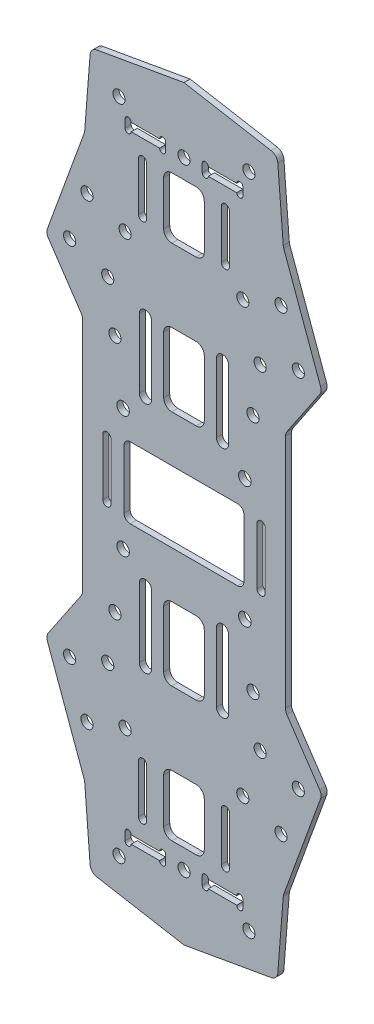
SolidWorks part; units mm, degrees
ref_plane "Front Plane" through (0, 0, 0) normal (0, 0, 1) x (1, 0, 0)
ref_plane "Top Plane" through (0, 0, 0) normal (0, 1, 0) x (1, 0, 0)
ref_plane "Right Plane" through (0, 0, 0) normal (1, 0, 0) x (0, 0, -1)
sketch "Sketch1" plane through (0, 0, 0) normal (0, 0, 1) x (1, 0, 0)
  line L0 (20, 7) -> (20, -7)
  line L1 (18, -7) -> (18, 7)
  line L2 (-18, 7) -> (-18, -7)
  line L3 (-20, -7) -> (-20, 7)
  line L4 (-11.2, -70.25) -> (-11.2, -58.25)
  line L5 (-9.2, -58.25) -> (-9.2, -70.25)
  line L6 (-11, -37.25) -> (-11, -20.25)
  line L7 (-8, -20.25) -> (-8, -37.25)
  line L8 (8, -37.25) -> (8, -20.25)
  line L9 (11, -20.25) -> (11, -37.25)
  line L10 (9.2, -70.25) -> (9.2, -58.25)
  line L11 (11.2, -58.25) -> (11.2, -70.25)
  line L12 (-3, -20.25) -> (3, -20.25)
  line L13 (5, -22.25) -> (5, -36.25)
  line L14 (3, -38.25) -> (-3, -38.25)
  line L15 (-5, -36.25) -> (-5, -22.25)
  line L16 (5, -58.25) -> (5, -69.25)
  line L17 (3, -71.25) -> (-3, -71.25)
  line L18 (-5, -69.25) -> (-5, -58.25)
  line L19 (-3, -56.25) -> (3, -56.25)
  line L20 (11.2, 70.25) -> (11.2, 58.25)
  line L21 (9.2, 58.25) -> (9.2, 70.25)
  line L22 (11, 37.25) -> (11, 20.25)
  line L23 (8, 20.25) -> (8, 37.25)
  line L24 (-8, 37.25) -> (-8, 20.25)
  line L25 (-11, 20.25) -> (-11, 37.25)
  line L26 (-9.2, 70.25) -> (-9.2, 58.25)
  line L27 (-11.2, 58.25) -> (-11.2, 70.25)
  line L28 (13.25, -8.75) -> (-13.25, -8.75)
  line L29 (-14.75, -7.25) -> (-14.75, 7.25)
  line L30 (-13.25, 8.75) -> (13.25, 8.75)
  line L31 (14.75, 7.25) -> (14.75, -7.25)
  line L32 (-5, 58.25) -> (-5, 69.25)
  line L33 (-3, 71.25) -> (3, 71.25)
  line L34 (5, 69.25) -> (5, 58.25)
  line L35 (3, 56.25) -> (-3, 56.25)
  line L36 (-3, 38.25) -> (3, 38.25)
  line L37 (5, 36.25) -> (5, 22.25)
  line L38 (3, 20.25) -> (-3, 20.25)
  line L39 (-5, 22.25) -> (-5, 36.25)
  line L40 (-24.5714, 68.9048) -> (-33.6515, 43.9576)
  line L41 (-33.4302, 42.1552) -> (-25.3419, 30.1639)
  line L42 (-25, 29.0455) -> (-25, -29.0455)
  line L43 (-25.3419, -30.1639) -> (-33.4302, -42.1552)
  line L44 (-33.6515, -43.9576) -> (-24.5714, -68.9048)
  line L45 (-24.457, -69.4319) -> (-23.1215, -86.4007)
  line L46 (-21.475, -88.2134) -> (0, -92)
  line L47 (0, -92) -> (21.475, -88.2134)
  line L48 (23.1215, -86.4007) -> (24.457, -69.4319)
  line L49 (24.5714, -68.9048) -> (33.6515, -43.9576)
  line L50 (33.4302, -42.1552) -> (25.3419, -30.1639)
  line L51 (25, -29.0455) -> (25, 29.0455)
  line L52 (25.3419, 30.1639) -> (33.4302, 42.1552)
  line L53 (33.6515, 43.9576) -> (24.5714, 68.9048)
  line L54 (24.457, 69.4319) -> (23.1215, 86.4007)
  line L55 (21.475, 88.2134) -> (0, 92)
  line L56 (0, 92) -> (-21.475, 88.2134)
  line L57 (-23.1215, 86.4007) -> (-24.457, 69.4319)
  line L58 (-14.5, 75) -> (-14.5, 77)
  line L59 (-13, 77) -> (-6, 77)
  line L60 (-4.5, 77) -> (-4.5, 75)
  line L61 (-6, 75) -> (-13, 75)
  line L62 (6, 77) -> (13, 77)
  line L63 (14.5, 77) -> (14.5, 75)
  line L64 (13, 75) -> (6, 75)
  line L65 (4.5, 75) -> (4.5, 77)
  line L66 (13, -77) -> (6, -77)
  line L67 (4.5, -77) -> (4.5, -75)
  line L68 (6, -75) -> (13, -75)
  line L69 (14.5, -75) -> (14.5, -77)
  line L70 (-6, -77) -> (-13, -77)
  line L71 (-14.5, -77) -> (-14.5, -75)
  line L72 (-13, -75) -> (-6, -75)
  line L73 (-4.5, -75) -> (-4.5, -77)
  arc A0 (20, -7) -> (18, -7) centre (19, -7) cw
  arc A1 (18, 7) -> (20, 7) centre (19, 7) cw
  arc A2 (-18, -7) -> (-20, -7) centre (-19, -7) cw
  arc A3 (-20, 7) -> (-18, 7) centre (-19, 7) cw
  arc A4 (-11.2, -58.25) -> (-9.2, -58.25) centre (-10.2, -58.25) cw
  arc A5 (-9.2, -70.25) -> (-11.2, -70.25) centre (-10.2, -70.25) cw
  arc A6 (-11, -20.25) -> (-8, -20.25) centre (-9.5, -20.25) cw
  arc A7 (-8, -37.25) -> (-11, -37.25) centre (-9.5, -37.25) cw
  arc A8 (8, -20.25) -> (11, -20.25) centre (9.5, -20.25) cw
  arc A9 (11, -37.25) -> (8, -37.25) centre (9.5, -37.25) cw
  arc A10 (9.2, -58.25) -> (11.2, -58.25) centre (10.2, -58.25) cw
  arc A11 (11.2, -70.25) -> (9.2, -70.25) centre (10.2, -70.25) cw
  arc A12 (3, -20.25) -> (5, -22.25) centre (3, -22.25) cw
  arc A13 (5, -36.25) -> (3, -38.25) centre (3, -36.25) cw
  arc A14 (-3, -38.25) -> (-5, -36.25) centre (-3, -36.25) cw
  arc A15 (-5, -22.25) -> (-3, -20.25) centre (-3, -22.25) cw
  arc A16 (5, -69.25) -> (3, -71.25) centre (3, -69.25) cw
  arc A17 (-3, -71.25) -> (-5, -69.25) centre (-3, -69.25) cw
  arc A18 (-5, -58.25) -> (-3, -56.25) centre (-3, -58.25) cw
  arc A19 (3, -56.25) -> (5, -58.25) centre (3, -58.25) cw
  arc A20 (11.2, 58.25) -> (9.2, 58.25) centre (10.2, 58.25) cw
  arc A21 (9.2, 70.25) -> (11.2, 70.25) centre (10.2, 70.25) cw
  arc A22 (11, 20.25) -> (8, 20.25) centre (9.5, 20.25) cw
  arc A23 (8, 37.25) -> (11, 37.25) centre (9.5, 37.25) cw
  arc A24 (-8, 20.25) -> (-11, 20.25) centre (-9.5, 20.25) cw
  arc A25 (-11, 37.25) -> (-8, 37.25) centre (-9.5, 37.25) cw
  arc A26 (-9.2, 58.25) -> (-11.2, 58.25) centre (-10.2, 58.25) cw
  arc A27 (-11.2, 70.25) -> (-9.2, 70.25) centre (-10.2, 70.25) cw
  arc A28 (-13.25, -8.75) -> (-14.75, -7.25) centre (-13.25, -7.25) cw
  arc A29 (-14.75, 7.25) -> (-13.25, 8.75) centre (-13.25, 7.25) cw
  arc A30 (13.25, 8.75) -> (14.75, 7.25) centre (13.25, 7.25) cw
  arc A31 (14.75, -7.25) -> (13.25, -8.75) centre (13.25, -7.25) cw
  arc A32 (-5, 69.25) -> (-3, 71.25) centre (-3, 69.25) cw
  arc A33 (3, 71.25) -> (5, 69.25) centre (3, 69.25) cw
  arc A34 (5, 58.25) -> (3, 56.25) centre (3, 58.25) cw
  arc A35 (-3, 56.25) -> (-5, 58.25) centre (-3, 58.25) cw
  arc A36 (3, 38.25) -> (5, 36.25) centre (3, 36.25) cw
  arc A37 (5, 22.25) -> (3, 20.25) centre (3, 22.25) cw
  arc A38 (-3, 20.25) -> (-5, 22.25) centre (-3, 22.25) cw
  arc A39 (-5, 36.25) -> (-3, 38.25) centre (-3, 36.25) cw
  arc A40 (-24.457, 69.4319) -> (-24.5714, 68.9048) centre (-26.4508, 69.5889) cw
  arc A41 (-33.6515, 43.9576) -> (-33.4302, 42.1552) centre (-31.7721, 43.2736) ccw
  arc A42 (-25.3419, 30.1639) -> (-25, 29.0455) centre (-27, 29.0455) cw
  arc A43 (-25, -29.0455) -> (-25.3419, -30.1639) centre (-27, -29.0455) cw
  arc A44 (-33.4302, -42.1552) -> (-33.6515, -43.9576) centre (-31.7721, -43.2736) ccw
  arc A45 (-24.5714, -68.9048) -> (-24.457, -69.4319) centre (-26.4508, -69.5889) cw
  arc A46 (-23.1215, -86.4007) -> (-21.475, -88.2134) centre (-21.1277, -86.2438) ccw
  arc A47 (21.475, -88.2134) -> (23.1215, -86.4007) centre (21.1277, -86.2438) ccw
  arc A48 (24.457, -69.4319) -> (24.5714, -68.9048) centre (26.4508, -69.5889) cw
  arc A49 (33.6515, -43.9576) -> (33.4302, -42.1552) centre (31.7721, -43.2736) ccw
  arc A50 (25.3419, -30.1639) -> (25, -29.0455) centre (27, -29.0455) cw
  arc A51 (25, 29.0455) -> (25.3419, 30.1639) centre (27, 29.0455) cw
  arc A52 (33.4302, 42.1552) -> (33.6515, 43.9576) centre (31.7721, 43.2736) ccw
  arc A53 (24.5714, 68.9048) -> (24.457, 69.4319) centre (26.4508, 69.5889) cw
  arc A54 (23.1215, 86.4007) -> (21.475, 88.2134) centre (21.1277, 86.2438) ccw
  arc A55 (-21.475, 88.2134) -> (-23.1215, 86.4007) centre (-21.1277, 86.2438) ccw
  circle A56 centre (-16, 81) radius 1.5
  circle A57 centre (0, 76) radius 1.5
  circle A58 centre (-28.1722, 44.6202) radius 1.5
  circle A59 centre (-23.8969, 56.3664) radius 1.5
  circle A60 centre (-18.7753, 41.2) radius 1.5
  circle A61 centre (-14.5, 52.9462) radius 1.5
  circle A62 centre (-17, 29.5) radius 1.5
  circle A63 centre (-15.25, 15.25) radius 1.5
  circle A64 centre (15.25, 15.25) radius 1.5
  circle A65 centre (17, 29.5) radius 1.5
  circle A66 centre (14.5, 52.9462) radius 1.5
  circle A67 centre (18.7753, 41.2) radius 1.5
  circle A68 centre (23.8969, 56.3664) radius 1.5
  circle A69 centre (28.1722, 44.6202) radius 1.5
  circle A70 centre (16, 81) radius 1.5
  circle A71 centre (16, -81) radius 1.5
  circle A72 centre (28.1722, -44.6202) radius 1.5
  circle A73 centre (23.8969, -56.3664) radius 1.5
  circle A74 centre (18.7753, -41.2) radius 1.5
  circle A75 centre (14.5, -52.9462) radius 1.5
  circle A76 centre (17, -29.5) radius 1.5
  circle A77 centre (15.25, -15.25) radius 1.5
  circle A78 centre (-15.25, -15.25) radius 1.5
  circle A79 centre (-17, -29.5) radius 1.5
  circle A80 centre (-14.5, -52.9462) radius 1.5
  circle A81 centre (-18.7753, -41.2) radius 1.5
  circle A82 centre (-23.8969, -56.3664) radius 1.5
  circle A83 centre (-28.1722, -44.6202) radius 1.5
  circle A84 centre (0, -76) radius 1.5
  circle A85 centre (-16, -81) radius 1.5
  arc A86 (-13, 75) -> (-14.5, 75) centre (-13.75, 75) cw
  arc A87 (-14.5, 77) -> (-13, 77) centre (-13.75, 77) cw
  arc A88 (-6, 77) -> (-4.5, 77) centre (-5.25, 77) cw
  arc A89 (-4.5, 75) -> (-6, 75) centre (-5.25, 75) cw
  arc A90 (4.5, 77) -> (6, 77) centre (5.25, 77) cw
  arc A91 (13, 77) -> (14.5, 77) centre (13.75, 77) cw
  arc A92 (14.5, 75) -> (13, 75) centre (13.75, 75) cw
  arc A93 (6, 75) -> (4.5, 75) centre (5.25, 75) cw
  arc A94 (14.5, -77) -> (13, -77) centre (13.75, -77) cw
  arc A95 (6, -77) -> (4.5, -77) centre (5.25, -77) cw
  arc A96 (4.5, -75) -> (6, -75) centre (5.25, -75) cw
  arc A97 (13, -75) -> (14.5, -75) centre (13.75, -75) cw
  arc A98 (-4.5, -77) -> (-6, -77) centre (-5.25, -77) cw
  arc A99 (-13, -77) -> (-14.5, -77) centre (-13.75, -77) cw
  arc A100 (-14.5, -75) -> (-13, -75) centre (-13.75, -75) cw
  arc A101 (-6, -75) -> (-4.5, -75) centre (-5.25, -75) cw
extrude "bottom-plate" add sketch "Sketch1" against normal blind 1.5
sketch "Sketch2" plane through (0, 0, 0) normal (0, 0, 1) x (1, 0, 0)
  circle A0 centre (-15.25, 15.25) radius 1.5 construction
  circle A1 centre (15.25, 15.25) radius 1.5 construction
  circle A2 centre (-15.25, -15.25) radius 1.5 construction
  circle A3 centre (15.25, -15.25) radius 1.5 construction
  circle A4 centre (-15.25, 15.25) radius 1.5
  circle A5 centre (15.25, 15.25) radius 1.5
  circle A6 centre (-15.25, -15.25) radius 1.5
  circle A7 centre (15.25, -15.25) radius 1.5
extrude "Boss-Extrude2" add sketch "Sketch2" against normal up to surface (1.5 mm away) up to face at (-9.5, -76, -1.5)
sketch "Sketch4" plane through (0, 0, 0) normal (0, 0, 1) x (1, 0, 0)
  line L0 (0, 92) -> (0, -92) construction
  line L1 (-25, 0) -> (25, 0) construction
  line L2 (-25, 29.0455) -> (-25, -29.0455) construction
  line L3 (25, -29.0455) -> (25, 29.0455) construction
  circle A0 centre (-15, 15) radius 1.55
  circle A1 centre (15, 15) radius 1.55
  circle A2 centre (15, -15) radius 1.55
  circle A3 centre (-15, -15) radius 1.55
  dimension "D1" = 3.1
  dimension "D2" = 30
  dimension "D3" = 30
extrude "Cut-Extrude1" cut sketch "Sketch4" against normal up to next
